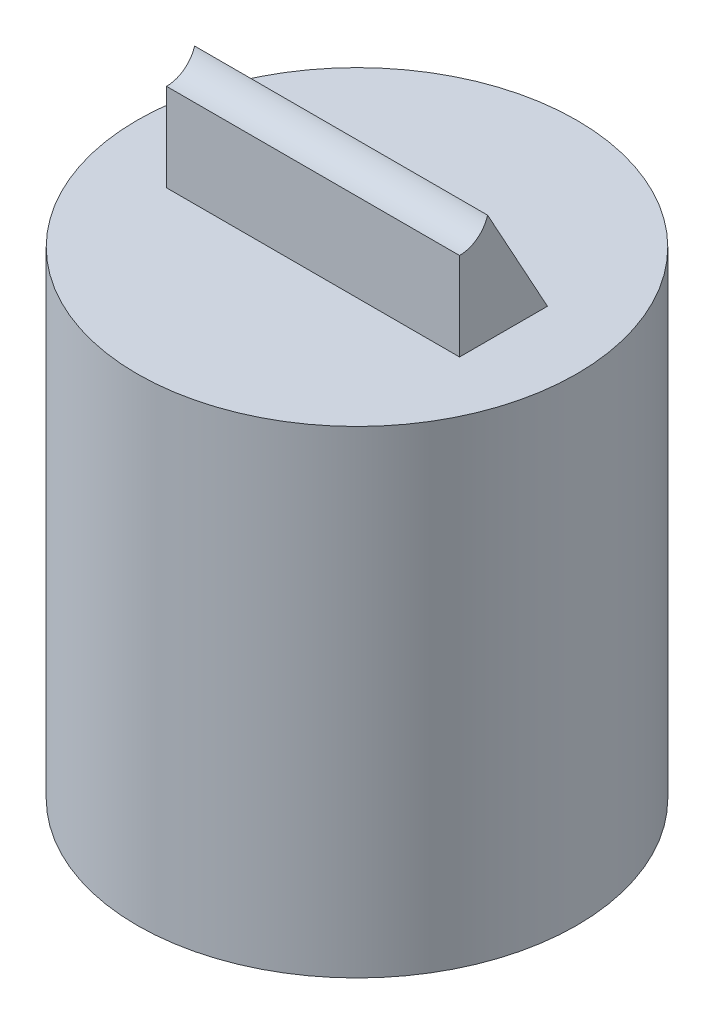
SolidWorks part; units mm, degrees
ref_plane "Ebene vorne" through (0, 0, 0) normal (0, 0, 1) x (1, 0, 0)
ref_plane "Ebene oben" through (0, 0, 0) normal (0, 1, 0) x (1, 0, 0)
ref_plane "Ebene rechts" through (0, 0, 0) normal (1, 0, 0) x (0, 0, -1)
sketch "Skizze1" plane through (0, 0, 0) normal (0, 1, 0) x (1, 0, 0)
  circle A0 centre (0, 0) radius 75
  dimension "D1" = 150
extrude "Aufsatz-Linear austragen1" add sketch "Skizze1" along normal blind 163
sketch "Skizze2" plane through (0, 163, 0) normal (0, 1, 0) x (1, 0, 0)
  line L1 (-50, 15) -> (50, 15)
  line L2 (-50, 15) -> (-50, -15)
  line L3 (-50, -15) -> (50, -15)
  line L4 (50, 15) -> (50, -15)
  line L5 (-50, 15) -> (50, -15) construction
  line L6 (-50, -15) -> (50, 15) construction
  point P0 (0, 0)
  dimension "D1" = 30
  dimension "D2" = 100
extrude "Aufsatz-Linear austragen2" add sketch "Skizze2" along normal blind 40
sketch "Skizze3" plane through (50, 0, 0) normal (1, 0, 0) x (0, 0, -1)
  circle A0 centre (-15, 203) radius 10
  dimension "D1" = 20
extrude "Schnitt-Linear austragen2" cut sketch "Skizze3" against normal blind 100 contours A0
sketch "Skizze4" plane through (50, 0, 0) normal (1, 0, 0) x (0, 0, -1)
  line L1 (15, 163) -> (15, 203)
  line L3 (15, 203) -> (-7, 203)
  line L4 (-7, 203) -> (15, 163)
  dimension "D1" = 22
extrude "Schnitt-Linear austragen3" cut sketch "Skizze4" against normal blind 100
